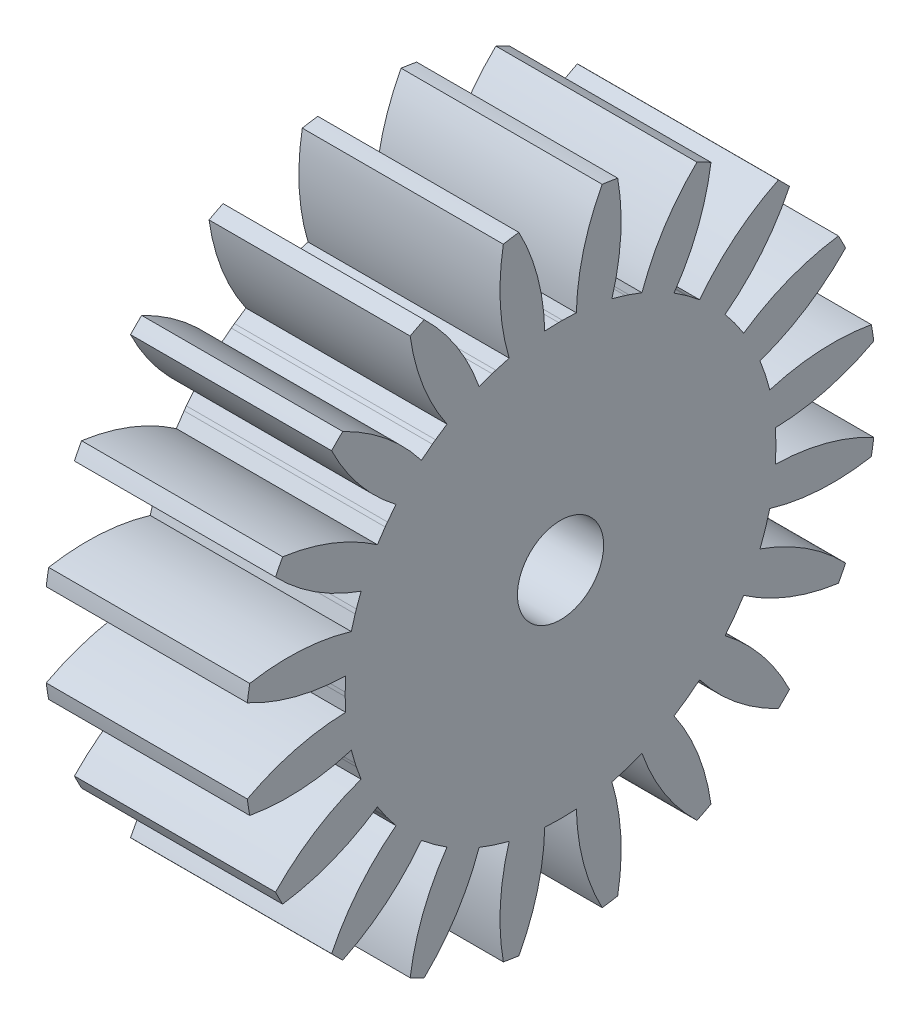
SolidWorks part; units mm, degrees
ref_plane "Front Plane" through (0, 0, 0) normal (0, 0, 1) x (1, 0, 0)
ref_plane "Top Plane" through (0, 0, 0) normal (0, 1, 0) x (1, 0, 0)
ref_plane "Right Plane" through (0, 0, 0) normal (1, 0, 0) x (0, 0, -1)
sketch "Sketch1" plane through (0, 0, 0) normal (1, 0, 0) x (0, 0, -1)
  circle A0 centre (0, 0) radius 110
  dimension "D1" = 220
extrude "Boss-Extrude1" add sketch "Sketch1" along normal mid plane 70
sketch "Sketch6" plane through (35, 0, 0) normal (1, 0, 0) x (0, 0, -1)
  circle A0 centre (0, 0) radius 15
  dimension "D1" = 30
extrude "Cut-Extrude4" cut sketch "Sketch6" against normal through all
sketch "Sketch7" plane through (35, 0, 0) normal (1, 0, 0) x (0, 0, -1)
  line L0 (0, 0) -> (0, 149.9703) construction
  line L1 (0, 74.9852) -> (-5.5, 74.7981)
  line L2 (0, 74.9852) -> (5.5, 74.7981)
  line L3 (-14.5, 109.0401) -> (0, 147)
  line L4 (14.5, 109.0401) -> (0, 147)
  circle A0 centre (0, 0) radius 75 construction
  circle A1 centre (0, 0) radius 90 construction
  arc A2 (-5.5, 74.7981) -> (-14.5, 109.0401) centre (-82.0985, 72.9691) ccw
  circle A3 centre (0, 0) radius 110 construction
  arc A4 (5.5, 74.7981) -> (14.5, 109.0401) centre (82.0985, 72.9691) cw
  point P12 (0, 37.4926)
  point P16 (0, 0)
  point P17 (0, 0)
  point P18 (0, 0)
  point P19 (0, 0)
  point P20 (-10.794, 72.2279)
  point P21 (-19.3804, 108.2793)
  point P22 (-6.5459, 74.9852)
  point P23 (0, 0)
  dimension "D1" = 180
  dimension "D2" = 150
  dimension "D3" = 11
  dimension "D4" = 29
  dimension "D6" = 147
extrude "Cut-Extrude5" cut sketch "Sketch7" against normal through all
fillet "Fillet1" radius 20 1 edges at (0, 74.9852, 0)
pattern_circular "CirPattern3" count 20 over 360 about axis through (35, 0, 0) along (1, 0, 0) of "Cut-Extrude5", "Fillet1"
